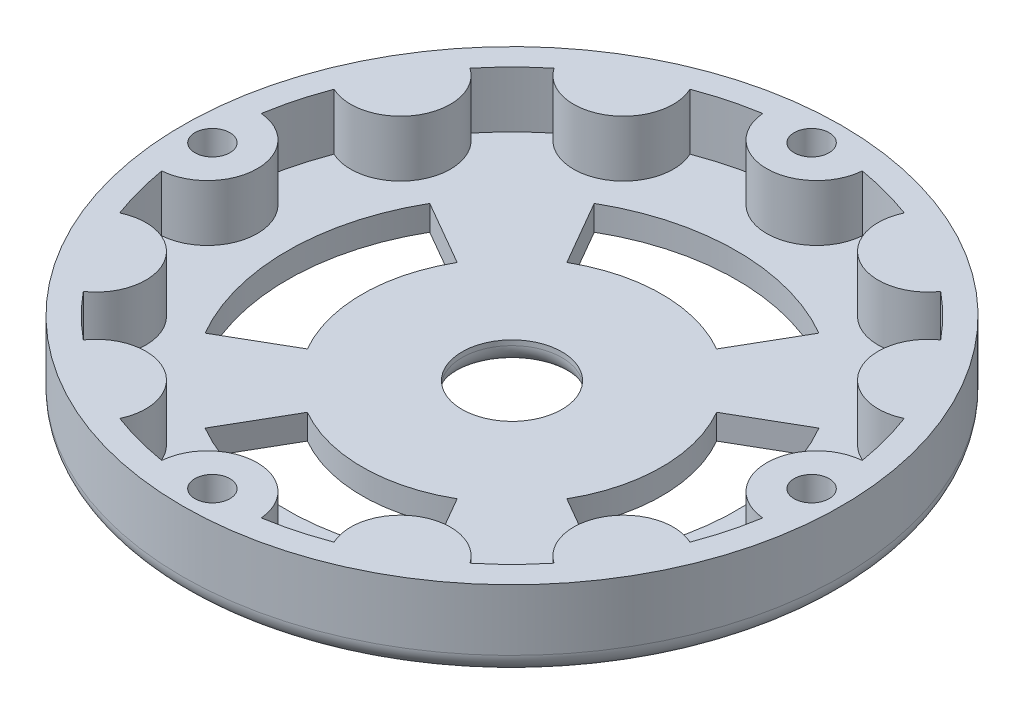
SolidWorks part; units mm, degrees
note: The reader was unsure of these and kept them because the rebuilt part matched: shared geometry of "Sketch1<8>".
material "PET"
ref_plane "Front Plane" through (0, 0, 0) normal (0, 0, 1) x (1, 0, 0)
ref_plane "Top Plane" through (0, 0, 0) normal (0, 1, 0) x (1, 0, 0)
ref_plane "Right Plane" through (0, 0, 0) normal (1, 0, 0) x (0, 0, -1)
sketch "Sketch1" plane through (0, 0, 0) normal (0, 1, 0) x (1, 0, 0)
  circle A0 centre (0, 0) radius 41.91
  circle A2 centre (0, 0) radius 38.735
  arc A3 (-6.3286, 38.2145) -> (6.3286, 38.2145) centre (0, 38.735) ccw
  circle A4 centre (0, 0) radius 41.91
  point P56 (0, 0)
  dimension "D1" = 12.7
  dimension "D2" = 77.47
  dimension "D3" = 0
  dimension "D4" = 3.175
extrude "Boss-Extrude3" add sketch "Sketch1" along normal blind 7.1501 contours A2 A3 | A2 A3 | A0
extrude "Boss-Extrude4" add sketch "Sketch1<8>" against normal blind 3.175 contours A3 A2 | A2 A3 | A2 A3 | A3 A2 A0
sketch "Sketch1<8>" plane through (0, 0, 0) normal (0, 1, 0) x (1, 0, 0) same geometry as "Sketch1"
sketch "Sketch3" plane through (0, 7.1501, 0) normal (0, -1, 0) x (1, 0, 0)
  circle A0 centre (0, 0) radius 6.35
  dimension "D1" = 12.7
extrude "Cut-Extrude1" cut sketch "Sketch3" along normal up to surface (10.3251 mm away) contours A0
pattern_circular "CirPattern1" count 12 over 360 about axis through (0, 0, 0) along (0, 1, 0) of "Boss-Extrude3"
fillet "Fillet1" radius 2.54 2 edges at (0, -3.175, 6.35) (0, -3.175, 41.91)
sketch "Sketch4" plane through (0, 7.1501, 0) normal (0, 1, 0) x (1, 0, 0)
  circle A0 centre (0, 0) radius 38.1 construction
  circle A1 centre (0, 38.1) radius 2.2225
  dimension "D1" = 76.2
  dimension "D2" = 4.445
extrude "Cut-Extrude2" cut sketch "Sketch4" against normal up to surface (10.3251 mm away) contours A1 up to face at (0, -3.175, 8.89)
pattern_circular "CirPattern2" count 4 over 360 about axis through (0, 0, 0) along (0, 1, 0) of "Cut-Extrude2"
scale "Scale1" scale about centroid uniform scaling yes scale factor 2
sketch "Sketch5" plane through (0, -0.4421, 0) normal (0, 1, 0) x (1, 0, 0)
  line L0 (-19.05, 32.9956) -> (-28.575, 49.4934)
  line L1 (19.05, 32.9956) -> (28.575, 49.4934)
  arc A0 (28.575, 49.4934) -> (-28.575, 49.4934) centre (0, 0) ccw
  arc A1 (19.05, 32.9956) -> (-19.05, 32.9956) centre (0, 0) ccw
  point P8 (0, 57.15)
  point P9 (0, 38.1)
  dimension "D1" = 60
  dimension "D2" = 38.1
  dimension "D3" = 19.05
extrude "Cut-Extrude3" cut sketch "Sketch5" against normal up to surface (6.35 mm away)
pattern_circular "CirPattern3" count 4 over 360 about axis through (0, -6.7921, 0) along (0, 1, 0) of "Cut-Extrude3"
scale "Scale2" scale about centroid uniform scaling yes scale factor 0.5
